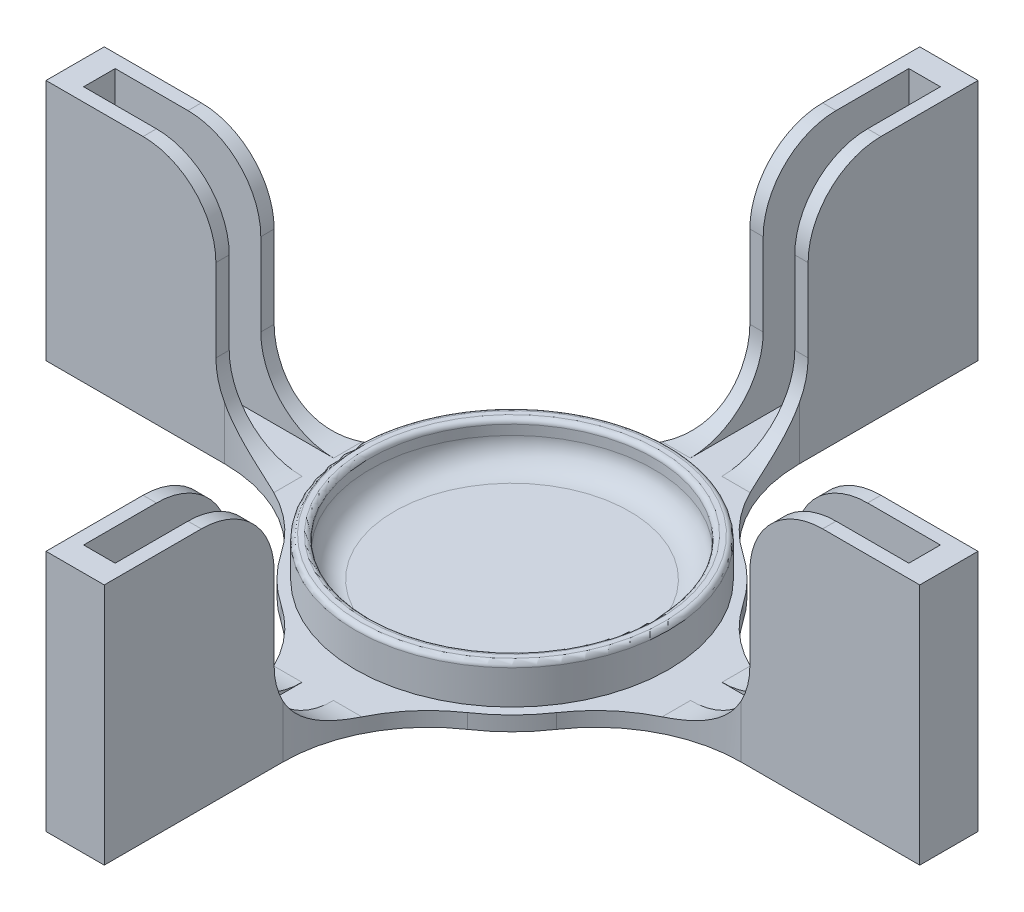
SolidWorks part; units mm, degrees
ref_plane "Front Plane" through (0, 0, 0) normal (0, 0, 1) x (1, 0, 0)
ref_plane "Top Plane" through (0, 0, 0) normal (0, 1, 0) x (1, 0, 0)
ref_plane "Right Plane" through (0, 0, 0) normal (1, 0, 0) x (0, 0, -1)
ref_plane "BASE THICKNESS" through (0, 3, 0) normal (0, 1, 0) x (1, 0, 0)
ref_plane "FIN HOLDER CRADDLE THICKNESS" through (0, 50, 0) normal (0, 1, 0) x (1, 0, 0)
ref_plane "TUBE ALIGNMENT INSERT" through (0, 11, 0) normal (0, 1, 0) x (1, 0, 0)
ref_axis "Axis1" through (0, 56.5, 0) along (0, -1, 0)
sketch "Sketch1" plane through (0, 0, 0) normal (0, 1, 0) x (1, 0, 0)
  circle A0 centre (0, 0) radius 34.25
  dimension "D1" = 68.5
extrude "BASE" add sketch "Sketch1" along normal up to surface (3 mm away) up to plane "BASE THICKNESS"
sketch "Sketch2" plane through (0, 0, 0) normal (0, 1, 0) x (1, 0, 0)
  line L1 (-6, 90) -> (6, 90)
  line L2 (-6, 90) -> (-6, 0)
  line L3 (-6, 0) -> (6, 0)
  line L4 (6, 90) -> (6, 0)
  dimension "D1" = 12
  dimension "D2" = 90
extrude "FIN EXTENSION BASE" add sketch "Sketch2" along normal up to surface (3 mm away) up to plane "BASE THICKNESS"
sketch "Sketch3" plane through (0, 0, 0) normal (0, 1, 0) x (1, 0, 0)
  line L0 (-6, 55) -> (-3.25, 55)
  line L1 (-3.25, 55) -> (-3.25, 85)
  line L2 (-3.25, 85) -> (3.25, 85)
  line L3 (3.25, 85) -> (3.25, 55)
  line L4 (3.25, 55) -> (6, 55)
  line L5 (6, 55) -> (6, 90)
  line L6 (6, 90) -> (-6, 90)
  line L7 (-6, 90) -> (-6, 55)
  dimension "D1" = 6.5
  dimension "D2" = 85
  dimension "D3" = 35
extrude "FIN CRADDLE" add sketch "Sketch3" along normal up to surface (50 mm away) up to plane "FIN HOLDER CRADDLE THICKNESS"
fillet "Fillet2" radius 30 2 edges at (6, 1.5, -33.7204) (-6, 1.5, -33.7204)
fillet "Fillet1" radius 15 4 edges at (-4.625, 50, -55) (4.625, 50, -55) (-4.625, 3, -55) (4.625, 3, -55)
pattern_circular "CirPattern1" count 4 over 360 about axis through (0, 56.5, 0) along (0, -1, 0) of "FIN EXTENSION BASE", "FIN CRADDLE", "Fillet2", "Fillet1"
sketch "Sketch4" plane through (0, 11, 0) normal (0, 1, 0) x (1, 0, 0)
  circle A0 centre (0, 0) radius 32.25
  circle A1 centre (0, 0) radius 29.25
  dimension "D1" = 64.5
  dimension "D2" = 3
extrude "Boss-Extrude5" add sketch "Sketch4" against normal up to surface (8 mm away) up to plane "BASE THICKNESS"
fillet "Fillet3" radius 5 1 edges at (0, 3, 29.25)
fillet "Fillet4" radius 1 2 edges at (0, 11, 29.25) (0, 11, 32.25)
